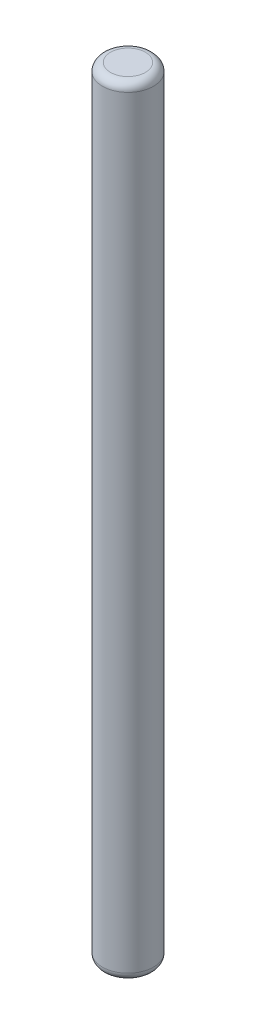
SolidWorks part; units mm, degrees
ref_plane "Front Plane" through (0, 0, 0) normal (0, 0, 1) x (1, 0, 0)
ref_plane "Top Plane" through (0, 0, 0) normal (0, 1, 0) x (1, 0, 0)
ref_plane "Right Plane" through (0, 0, 0) normal (1, 0, 0) x (0, 0, -1)
sketch "Sketch1" plane through (0, 0, 0) normal (0, 1, 0) x (1, 0, 0)
  circle A0 centre (0, 0) radius 3.175
  dimension "D1" = 6.35
extrude "Boss-Extrude1" add sketch "Sketch1" along normal blind 97
sketch "Sketch2" plane through (0, 97, 0) normal (0, 1, 0) x (1, 0, 0)
  line L0 (-1.6107, 2.7361) -> (1.5629, 2.7637)
  circle A0 centre (0, 0) radius 3.175 construction
  dimension "D1" = 2.75
extrude "Cut-Extrude1" cut sketch "Sketch2" against normal blind 21 and the other way through all
fillet "Fillet1" radius 1 2 edges at (0, 0, 3.175) (0.0276, 97, 3.1749)
